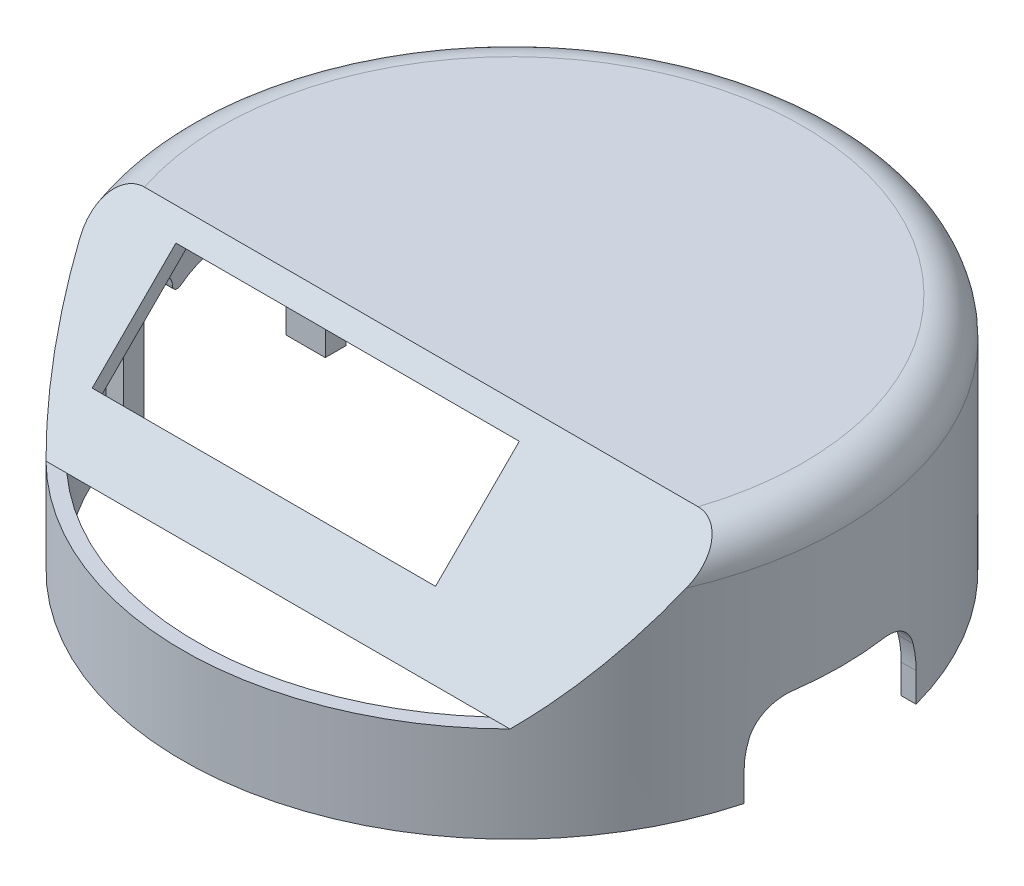
SolidWorks part; units mm, degrees
ref_plane "Front Plane" through (0, 0, 0) normal (0, 0, 1) x (1, 0, 0)
ref_plane "Top Plane" through (0, 0, 0) normal (0, 1, 0) x (1, 0, 0)
ref_plane "Right Plane" through (0, 0, 0) normal (1, 0, 0) x (0, 0, -1)
sketch "Sketch1" plane through (0, 0, 0) normal (0, 1, 0) x (1, 0, 0)
  circle A0 centre (0, 0) radius 69
  circle A1 centre (0, 0) radius 66
  dimension "D1" = 138
  dimension "D2" = 3
extrude "Boss-Extrude1" add sketch "Sketch1" along normal blind 40
sketch "Sketch13" plane through (0, 0, 0) normal (0, 0, 1) x (1, 0, 0)
  line L0 (66, 40) -> (-66, 40) construction
  line L5 (61, 50) -> (0, 50)
  line L7 (61, 47) -> (0, 47)
  line L8 (0, 50) -> (0, 47)
  line L11 (66, 42) -> (66, 40)
  line L12 (66, 40) -> (69, 40)
  line L13 (69, 42) -> (69, 40)
  arc A0 (66, 42) -> (61, 47) centre (61, 42) ccw
  arc A1 (69, 42) -> (61, 50) centre (61, 42) ccw
  point P14 (69, 50)
  dimension "D5" = 5
  dimension "D6" = 8
  dimension "D7" = 2
  dimension "D1" = 10
  dimension "D2" = 3
  dimension "D3" = 3
  dimension "D4" = 0
  dimension "D8" = 2
sketch "Sketch4" plane through (0, 0, 0) normal (1, 0, 0) x (0, 0, -1)
  line L1 (23.3, 0) -> (53.9, 0)
  line L2 (23.3, 0) -> (23.3, 30.6)
  line L3 (23.3, 30.6) -> (53.9, 30.6)
  line L4 (53.9, 0) -> (53.9, 30.6)
  dimension "D1" = 30.6
  dimension "D2" = 30.6
  dimension "D3" = 0
  dimension "D4" = 23.3
extrude "Cut-Extrude2" cut sketch "Sketch4" against normal through all
sketch "Sketch5" plane through (0, 0, 0) normal (1, 0, 0) x (0, 0, -1)
  line L8 (19, 13) -> (19, -6)
  line L9 (19, -6) -> (-19, -6)
  line L10 (-19, -6) -> (-19, 13)
  arc A1 (19, 13) -> (-19, 13) centre (0, 13) ccw
  dimension "D1" = 19
  dimension "D3" = 13
  dimension "D2" = 19
extrude "Cut-Extrude6" cut sketch "Sketch5" against normal through all
sketch "Sketch6" plane through (0, 0, 0) normal (1, 0, 0) x (0, 0, -1)
  line L0 (19, 13) -> (19, 0)
  line L2 (-19, 0) -> (-19, 13)
  line L3 (23.3, 13) -> (23.3, 0)
  line L4 (-23.3, 0) -> (-23.3, 13)
  line L5 (23.3, 0) -> (19, 0)
  line L6 (-19, 0) -> (-23.3, 0)
  arc A0 (19, 13) -> (-19, 13) centre (0, 13) ccw
  arc A1 (23.3, 13) -> (-23.3, 13) centre (0, 13) ccw
  dimension "D1" = 19
  dimension "D3" = 0
  dimension "D2" = 4.3
extrude "Boss-Extrude2" add sketch "Sketch6" against normal up to next from offset 58.1 offset against normal yes
sketch "Sketch7" plane through (-58.1, 0, 0) normal (1, 0, 0) x (0, 0, -1)
  line L0 (0, 36.3) -> (15, 36.3) construction
  arc A0 (23.3, 13) -> (-23.3, 13) centre (0, 13) ccw construction
  dimension "D1" = 15
ref_plane "Plane2" through (-10.9, -10.9, 0) normal (-0.7071, -0.7071, 0) x (0, 0, -1)
sketch "Sketch8" plane through (-10.9, -10.9, 0) normal (-0.7071, -0.7071, 0) x (0, 0, -1)
  line L0 (23.3, -41.0829) -> (23.3, -50.2753) construction
  line L1 (-23.3, -84.0829) -> (23.3, -84.0829)
  line L2 (-23.3, -84.0829) -> (-23.3, -49.0829)
  line L3 (-23.3, -49.0829) -> (23.3, -49.0829)
  line L4 (23.3, -84.0829) -> (23.3, -49.0829)
  line L5 (-23.3, -50.2753) -> (-23.3, -41.0829) construction
  line L6 (19, -41.0829) -> (23.3, -41.0829) construction
  dimension "D1" = 0
  dimension "D2" = 0
  dimension "D3" = 8
  dimension "D4" = 35
extrude "Boss-Extrude4" add sketch "Sketch8" along normal blind 30 contours L2 L1 L4 L3
sketch "Sketch9" plane through (0, 0, 0) normal (0, -1, 0) x (1, 0, 0)
  line L0 (-58.1, -23.3) -> (-61.7504, -23.3)
  line L1 (-64.947, -23.3) -> (-58.1, -23.3) construction
  line L6 (-38.0892, -53.9) -> (-43.0789, -53.9)
  line L7 (-38.0892, -53.9) -> (-43.0789, -53.9)
  line L12 (-66.3325, 19) -> (-58.1, 19)
  line L14 (-58.1, 19) -> (-58.1, 23.3)
  line L15 (-58.1, 23.3) -> (-61.7504, 23.3)
  line L18 (-58.1, 19) -> (-58.1, 23.3)
  line L19 (-58.1, 23.3) -> (-61.7504, 23.3)
  line L20 (-58.1, 19) -> (-58.1, -19)
  line L24 (-58.1, -19) -> (-66.3325, -19)
  line L25 (-64.947, -23.3) -> (-58.1, -23.3)
  line L27 (-58.1, -23.3) -> (-58.1, -19)
  line L31 (-58.1, -23.3) -> (-58.1, -19)
  arc A6 (-43.0789, -53.9) -> (-66.3325, 19) centre (0, 0) ccw
  arc A7 (-38.0892, -53.9) -> (-61.7504, 23.3) centre (0, 0) ccw
  arc A8 (-43.0789, -53.9) -> (-66.3325, 19) centre (0, 0) ccw
  arc A9 (-38.0892, -53.9) -> (-61.7504, 23.3) centre (0, 0) ccw
  arc A10 (-66.3325, -19) -> (-66.3325, 19) centre (0, 0) ccw
  arc A11 (-61.7504, -23.3) -> (-61.7504, 23.3) centre (0, 0) ccw
  arc A12 (-66.3325, -19) -> (-64.947, -23.3) centre (0, 0) ccw
  arc A14 (-66.3325, -19) -> (-64.947, -23.3) centre (0, 0) ccw
  circle A16 centre (0, 0) radius 69
  arc A18 (-61.7504, -23.3) -> (-61.7504, 23.3) centre (0, 0) ccw
  line M15 (-66.3325, 19) -> (-58.1, 19)
  line M16 (-58.1, 19) -> (-58.1, 23.3)
  line M17 (-58.1, 23.3) -> (-61.7504, 23.3)
  arc M18 (-61.7504, 23.3) -> (-38.0892, -53.9) centre (0, 0) cw
  dimension "D1" = 0
  dimension "D2" = 0
extrude "Cut-Extrude7" cut sketch "Sketch9" against normal through all flip side to cut contours A16
sketch "Sketch14" plane through (0, 40, 0) normal (0, 1, 0) x (1, 0, 0)
  circle A0 centre (0, 0) radius 69
  dimension "D1" = 138
extrude "Cut-Extrude13" cut sketch "Sketch14" along normal through all
extrude "Cut-Extrude8" cut sketch "Sketch9<3>" against normal through all contours L31 A11 M15 M18 M17 M16 region at (1.3919, 0, 0)
sketch "Sketch9<3>" plane through (0, 0, 0) normal (0, -1, 0) x (1, 0, 0) same geometry as "Sketch9"
extrude "Cut-Extrude9" cut sketch "Sketch5<2>" against normal through all
sketch "Sketch5<2>" plane through (0, 0, 0) normal (1, 0, 0) x (0, 0, -1) same geometry as "Sketch5"
sketch "Sketch11" plane through (-58.1, 0, 0) normal (1, 0, 0) x (0, 0, -1)
  line L0 (-19, 29) -> (-19, 11)
  line L1 (-19, 0) -> (-19, 13) construction
  line L2 (-19, 11) -> (-13, 11)
  line L3 (-13, 11) -> (-13, 29)
  line L4 (13, 29) -> (13, 11)
  line L5 (19, 29) -> (19, 11)
  line L6 (19, 13) -> (19, 0) construction
  line L7 (13, 11) -> (19, 11)
  arc A0 (19, 29) -> (13, 29) centre (16, 29) ccw
  arc A1 (-13, 29) -> (-19, 29) centre (-16, 29) ccw
  dimension "D1" = 6
  dimension "D2" = 6
  dimension "D3" = 18
  dimension "D4" = 18
extrude "Cut-Extrude11" cut sketch "Sketch11" against normal blind 4
fillet "Fillet3" radius 1 2 edges at (-60.1, 26.8564, -13) (-60.1, 26.8564, 13)
sketch "Sketch12" plane through (0, 0, 0) normal (1, 0, 0) x (0, 0, -1)
  line L39 (-18, -0.9) -> (18, -0.9)
  line L42 (18, -0.9) -> (18, 6.1)
  line L43 (9.5394, 17.1) -> (-9.5394, 17.1)
  line L44 (-18, 6.1) -> (-18, -0.9)
  line L45 (18, -0.9) -> (18, 6.1)
  line L46 (9.5394, 17.1) -> (-9.5394, 17.1)
  line L47 (-18, 6.1) -> (-18, -0.9)
  arc A58 (18, 6.1) -> (17.1709, 11.5) centre (0, 6.1) ccw
  arc A59 (17.1709, 11.5) -> (9.5394, 17.1) centre (9.5394, 9.1) ccw
  arc A60 (-17.1709, 11.5) -> (-18, 6.1) centre (0, 6.1) ccw
  arc A61 (-9.5394, 17.1) -> (-17.1709, 11.5) centre (-9.5394, 9.1) ccw
  arc A62 (18, 6.1) -> (17.1709, 11.5) centre (0, 6.1) ccw
  arc A63 (17.1709, 11.5) -> (9.5394, 17.1) centre (9.5394, 9.1) ccw
  arc A64 (-17.1709, 11.5) -> (-18, 6.1) centre (0, 6.1) ccw
  arc A65 (-9.5394, 17.1) -> (-17.1709, 11.5) centre (-9.5394, 9.1) ccw
  dimension "D1" = 0
extrude "Cut-Extrude12" cut sketch "Sketch12" along normal through all
revolve "Revolve2" add sketch "Sketch13" angle 360 about L8
sketch "Sketch15" plane through (0, 0, 0) normal (1, 0, 0) x (0, 0, -1)
  line L0 (-69, 20) -> (-49, 20)
  line L1 (-69, 42) -> (-69, 0) construction
  line L2 (-49, 20) -> (-19, 50)
  line L3 (61, 50) -> (-61, 50) construction
  line L12 (61, 50) -> (-61, 50)
  line L13 (-69, 42) -> (-69, 0)
  line L14 (-19, 50) -> (-61, 50)
  line L15 (-69, 42) -> (-69, 20)
  arc A4 (-61, 50) -> (-69, 42) centre (-61, 42) ccw
  arc A5 (-61, 50) -> (-69, 42) centre (-61, 42) ccw
  dimension "D1" = 0
  dimension "D2" = 20
  dimension "D3" = 45
  dimension "D4" = 50
extrude "Cut-Extrude14" cut sketch "Sketch15" against normal through all both and the other way through all
sketch "Sketch16" plane through (0, 34.5, 34.5) normal (0, 0.7071, 0.7071) x (1, 0, 0)
  line L0 (48.5798, -20.5061) -> (-48.5798, -20.5061)
  line L8 (44.2154, -20.5061) -> (48.5798, -20.5061)
  line L9 (57.9655, 21.9203) -> (-57.9655, 21.9203)
  line L10 (-48.5798, -20.5061) -> (-44.2154, -20.5061)
  line L11 (-56.8946, 17.6777) -> (56.8946, 17.6777)
  line L13 (57.9655, 21.9203) -> (-57.9655, 21.9203)
  ellipse E8 centre (0, 48.7904) end of major axis (0, -44.5477) minor radius 66 (44.2154, -20.5061) -> (60.2246, 10.6066) ccw
  ellipse E9 centre (0, 48.7904) end of major axis (0, -48.7904) minor radius 69 (48.5798, -20.5061) -> (63.498, 10.6066) ccw
  ellipse E10 centre (0, 48.7904) end of major axis (0, -48.7904) minor radius 69 (-63.498, 10.6066) -> (-48.5798, -20.5061) ccw
  ellipse E11 centre (0, 48.7904) end of major axis (0, -44.5477) minor radius 66 (-60.2246, 10.6066) -> (-44.2154, -20.5061) ccw
  ellipse E13 centre (0, 48.7904) end of major axis (0, -48.7904) minor radius 69 (48.5798, -20.5061) -> (63.498, 10.6066) ccw
  ellipse E14 centre (0, 48.7904) end of major axis (0, -48.7904) minor radius 69 (-63.498, 10.6066) -> (-48.5798, -20.5061) ccw
  spline S8 degree 3 poles (3912.1906, -1060.19) (-474.0428, -7.7638) (52.8952, -55.4422) (64.0117, 13.005) (64.0678, 13.6148) (64.0853, 14.8302) (64.0474, 15.4374) (63.9053, 16.3475) (63.8435, 16.6501) (63.691, 17.242) (63.6001, 17.5329) (63.3863, 18.1034) (63.2633, 18.3831) (62.9807, 18.9296) (62.8214, 19.1953) (62.4706, 19.6976) (62.2784, 19.936) (61.8562, 20.3843) (61.6266, 20.593) (61.1424, 20.9659) (60.8862, 21.1319) (60.3436, 21.4207) (60.0572, 21.5427) (59.4785, 21.7333) (59.1834, 21.8037) (35.687, 25.4579) (-35.6646, -112.0332) (4053.7208, -88.864) knots -13.861692 -13.861692 -13.861692 -13.861692 0.125 0.125 0.25 0.25 0.375 0.375 0.4375 0.4375 0.5 0.5 0.5625 0.5625 0.625 0.625 0.6875 0.6875 0.75 0.75 0.8125 0.8125 0.875 0.875 0.9375 0.9375 5.758932 5.758932 5.758932 5.758932 only from (63.498, 10.6066) to (57.9655, 21.9203)
  spline S9 degree 3 poles (-205.6627, 4017.4498) (51.5127, -403.5061) (-18.445, 28.1286) (-59.1848, 21.8036) (-59.488, 21.7309) (-60.0688, 21.5382) (-60.349, 21.4181) (-60.889, 21.1301) (-61.1508, 20.9602) (-61.6363, 20.5848) (-61.8618, 20.3787) (-62.281, 19.9328) (-62.4759, 19.6908) (-63.0028, 18.934) (-63.2792, 18.39) (-63.6025, 17.526) (-63.6943, 17.2307) (-63.8461, 16.6384) (-63.9067, 16.3397) (-64.0004, 15.7376) (-64.0334, 15.4343) (-64.0738, 14.8233) (-64.0811, 14.5144) (-64.0667, 13.5953) (-64.0096, 12.9894) (-51.0615, -66.3797) (666.3828, -43.4638) (-3974.0862, -793.7867) knots -8.261367 -8.261367 -8.261367 -8.261367 0.0625 0.0625 0.125 0.125 0.1875 0.1875 0.25 0.25 0.3125 0.3125 0.375 0.375 0.5 0.5 0.5625 0.5625 0.625 0.625 0.6875 0.6875 0.75 0.75 0.875 0.875 17.284586 17.284586 17.284586 17.284586 only from (-57.9655, 21.9203) to (-63.498, 10.6066)
  spline S10 degree 3 poles (-1013.6792, -290.9297) (139.5196, -14.3922) (-54.4741, -21.0966) (-60.572, 12.0934) (-60.6164, 12.4764) (-60.6461, 13.2376) (-60.632, 13.6168) (-60.5343, 14.3715) (-60.4493, 14.7502) (-60.2613, 15.2894) (-60.1885, 15.4651) (-60.0199, 15.8075) (-59.9233, 15.9753) (-59.7081, 16.2932) (-59.5897, 16.4432) (-59.3298, 16.7237) (-59.1866, 16.8552) (-58.8834, 17.0893) (-58.7234, 17.1923) (-58.3865, 17.3702) (-58.2077, 17.4456) (-57.8424, 17.5638) (-57.6566, 17.6069) (-45.8526, 19.389) (-18.5991, -34.513) (-1056.0111, 58.6202) knots -10.799953 -10.799953 -10.799953 -10.799953 0.125 0.125 0.25 0.25 0.375 0.375 0.5 0.5 0.5625 0.5625 0.625 0.625 0.6875 0.6875 0.75 0.75 0.8125 0.8125 0.875 0.875 0.9375 0.9375 4.787541 4.787541 4.787541 4.787541 only from (-60.2246, 10.6066) to (-56.8946, 17.6777)
  spline S11 degree 3 poles (105.4895, 1016.496) (0.843, -137.0603) (37.8292, 20.5931) (57.6559, 17.6071) (57.8452, 17.5631) (58.2102, 17.4446) (58.3857, 17.3706) (58.7229, 17.1927) (58.8858, 17.0877) (59.19, 16.8524) (59.3304, 16.7231) (59.5897, 16.4432) (59.7093, 16.2916) (60.0327, 15.8134) (60.1983, 15.4704) (60.3875, 14.9273) (60.4404, 14.7413) (60.5259, 14.369) (60.5589, 14.1815) (60.6321, 13.6154) (60.6462, 13.2306) (59.4361, -16.9384) (-113.5054, -18.3168) (1029.008, -237.2814) knots -6.426175 -6.426175 -6.426175 -6.426175 0.0625 0.0625 0.125 0.125 0.1875 0.1875 0.25 0.25 0.3125 0.3125 0.375 0.375 0.5 0.5 0.5625 0.5625 0.625 0.625 0.75 0.75 10.489773 10.489773 10.489773 10.489773 only from (56.8946, 17.6777) to (60.2246, 10.6066)
  spline S12 degree 3 poles (63.498, 10.6066) (63.675, 11.1953) (63.8147, 11.7924) (64.0117, 13.005) (64.0678, 13.6148) (64.0853, 14.8302) (64.0474, 15.4374) (63.9053, 16.3475) (63.8435, 16.6501) (63.691, 17.242) (63.6001, 17.5329) (63.3863, 18.1034) (63.2633, 18.3831) (62.9807, 18.9296) (62.8214, 19.1953) (62.4706, 19.6976) (62.2784, 19.936) (61.8562, 20.3843) (61.6266, 20.593) (61.1424, 20.9659) (60.8862, 21.1319) (60.3436, 21.4207) (60.0572, 21.5427) (59.4785, 21.7333) (59.1834, 21.8037) (58.582, 21.8973) (58.2732, 21.9203) (57.9655, 21.9203) knots 0 0 0 0 0.125 0.125 0.25 0.25 0.375 0.375 0.4375 0.4375 0.5 0.5 0.5625 0.5625 0.625 0.625 0.6875 0.6875 0.75 0.75 0.8125 0.8125 0.875 0.875 0.9375 0.9375 1 1 1 1
  spline S13 degree 3 poles (-57.9655, 21.9203) (-58.2723, 21.9203) (-58.5776, 21.8979) (-59.1848, 21.8036) (-59.488, 21.7309) (-60.0688, 21.5382) (-60.349, 21.4181) (-60.889, 21.1301) (-61.1508, 20.9602) (-61.6363, 20.5848) (-61.8618, 20.3787) (-62.281, 19.9328) (-62.4759, 19.6908) (-63.0028, 18.934) (-63.2792, 18.39) (-63.6025, 17.526) (-63.6943, 17.2307) (-63.8461, 16.6384) (-63.9067, 16.3397) (-64.0004, 15.7376) (-64.0334, 15.4343) (-64.0738, 14.8233) (-64.0811, 14.5144) (-64.0667, 13.5953) (-64.0096, 12.9894) (-63.8138, 11.7893) (-63.675, 11.1952) (-63.498, 10.6066) knots 0 0 0 0 0.0625 0.0625 0.125 0.125 0.1875 0.1875 0.25 0.25 0.3125 0.3125 0.375 0.375 0.5 0.5 0.5625 0.5625 0.625 0.625 0.6875 0.6875 0.75 0.75 0.875 0.875 1 1 1 1
  dimension "D1" = 0
extrude "Boss-Extrude5" add sketch "Sketch16" against normal blind 3
sketch "Sketch17" plane through (0, 34.5, 34.5) normal (0, 0.7071, 0.7071) x (1, 0, 0)
  line L0 (-47.23, 16.7777) -> (23.25, 16.7777) construction
  line L1 (-47.95, 17.0777) -> (23.95, 17.0777)
  line L2 (-47.95, 17.0777) -> (-47.95, -7.7223)
  line L3 (-47.95, -7.7223) -> (23.95, -7.7223)
  line L4 (23.95, 17.0777) -> (23.95, -7.7223)
  line L5 (-47.65, -7.0023) -> (-47.65, 16.3577) construction
  line L6 (23.23, -7.4223) -> (-47.23, -7.4223) construction
  line L7 (23.65, 16.3777) -> (23.65, -7.0023) construction
  dimension "D1" = 0.3
  dimension "D2" = 0.3
  dimension "D3" = 0.3
  dimension "D4" = 0.3
extrude "Cut-Extrude15" cut sketch "Sketch17" against normal through all
